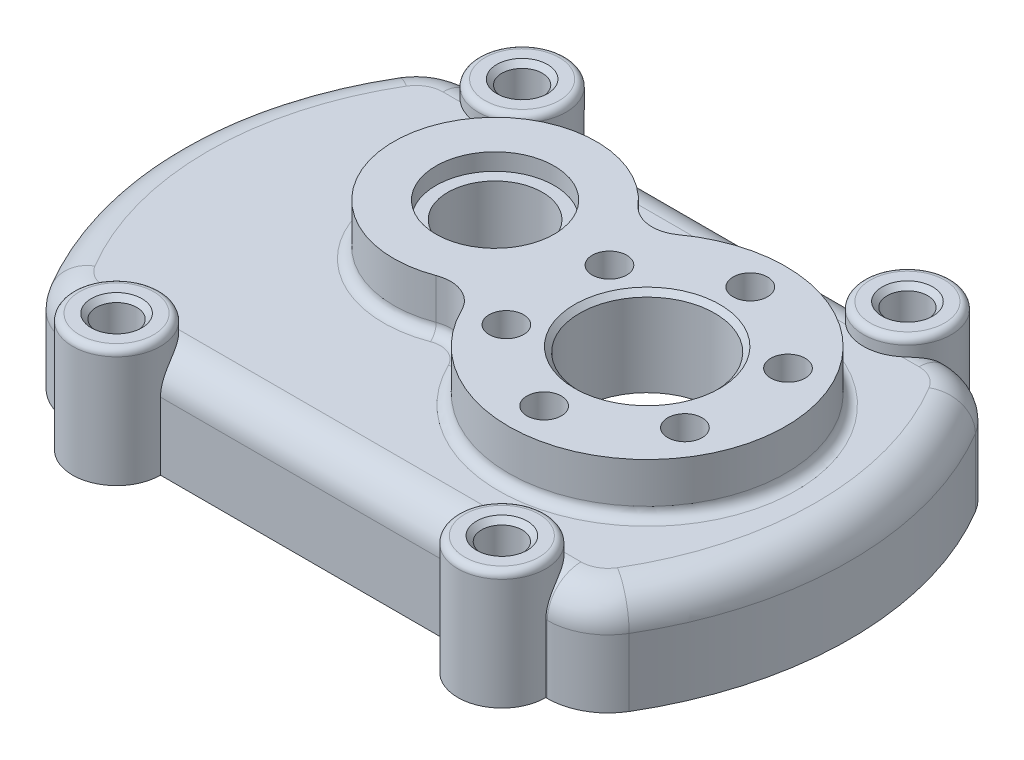
SolidWorks part; units mm, degrees
ref_plane "Piano frontale" through (0, 0, 0) normal (0, 0, 1) x (1, 0, 0)
ref_plane "Piano superiore" through (0, 0, 0) normal (0, 1, 0) x (1, 0, 0)
ref_plane "Piano destro" through (0, 0, 0) normal (1, 0, 0) x (0, 0, -1)
sketch "Schizzo2" plane through (0, 0, 0) normal (0, 1, 0) x (1, 0, 0)
  line L0 (0, 100) -> (0, -100) construction
  line L1 (-57, 100) -> (-57, -100) construction
  line L2 (57, 100) -> (57, -100) construction
  line L3 (-100, 0) -> (100, 0) construction
  line L5 (-80, -60) -> (80, -60)
  line L7 (-80, 60) -> (80, 60)
  line L9 (-80, -60) -> (80, 60) construction
  line L10 (-80, 60) -> (80, -60) construction
  arc A0 (80, 60) -> (80, -60) centre (0, 0) cw
  arc A1 (-80, 60) -> (-80, -60) centre (0, 0) ccw
  point P2 (0, 0)
  point P8 (-57, 0)
  point P9 (57, 0)
  point P12 (0, 0)
  point P13 (0, 0)
  dimension "D5" = 100
  dimension "D1" = 114
  dimension "D2" = 57
  dimension "D3" = 200
  dimension "D4" = 43
  dimension "D6" = 120
extrude "Estrusione-Estrusione3" add sketch "Schizzo2" against normal blind 30
sketch "Schizzo5" plane through (0, -30, 0) normal (0, -1, 0) x (1, 0, 0)
  line L0 (-100, 0) -> (100, 0) construction
  line L1 (-78.1665, -54) -> (78.1665, -54)
  line L3 (-78.1665, 54) -> (78.1665, 54)
  line L5 (-78.1665, -54) -> (78.1665, 54) construction
  line L6 (-78.1665, 54) -> (78.1665, -54) construction
  line L7 (-80, 60) -> (80, 60) construction
  arc A0 (-80, 60) -> (-80, -60) centre (0, 0) ccw construction
  arc A1 (78.1665, 54) -> (78.1665, -54) centre (-6, 0) cw
  arc A2 (-78.1665, 54) -> (-78.1665, -54) centre (6, 0) ccw
  point P0 (0, 0)
  point P8 (0, 0)
  point P10 (94, 0)
  point P16 (-94, 0)
  dimension "D1" = 100
  dimension "D2" = 6
  dimension "D3" = 6
extrude "Taglio-Estrusione1" cut sketch "Schizzo5" against normal blind 24
sketch "Schizzo6" plane through (0, 0, 0) normal (0, 1, 0) x (1, 0, 0)
  line L0 (-57, 100) -> (-57, -100) construction
  line L1 (-80, 60) -> (80, 60) construction
  circle A0 centre (-57, 60) radius 13
  circle A1 centre (-57, 60) radius 6
  dimension "D1" = 26
  dimension "D2" = 12
extrude "Estrusione-Estrusione4" add sketch "Schizzo6" along normal blind 5 and the other way blind 30
extrude "Taglio-Estrusione2" cut sketch "Schizzo6<3>" against normal up to next contours A1
sketch "Schizzo6<3>" plane through (0, 0, 0) normal (0, 1, 0) x (1, 0, 0) same geometry as "Schizzo6"
pattern_linear "Ripetizione a L1" count 2 spacing 114 along (1, 0, 0) of "Estrusione-Estrusione4", "Taglio-Estrusione2"
mirror "Specchia1" about plane through (0, 0, 0) normal (0, 0, 1) of "Ripetizione a L1"
sketch "Schizzo7" plane through (0, 0, 0) normal (0, 1, 0) x (1, 0, 0)
  line L0 (57, 100) -> (57, -100) construction
  line L4 (-80, 60) -> (80, 60) construction
  arc A0 (2.5862, 34.7449) -> (-9.3627, -13.0508) centre (-20, 15) ccw
  arc A1 (3.1668, -18.0087) -> (15.9748, 33.2233) centre (40, 0) ccw
  arc A2 (2.5862, 34.7449) -> (15.9748, 33.2233) centre (10.115, 41.3266) ccw
  arc A3 (-9.3627, -13.0508) -> (3.1668, -18.0087) centre (-5.8169, -22.4011) cw
  circle A6 centre (40, 0) radius 30.5 construction
  circle A7 centre (40, 0) radius 25
  circle A8 centre (-20, 15) radius 19
  dimension "D1" = 60
  dimension "D2" = 82
  dimension "D5" = 10
  dimension "D8" = 61
  dimension "D9" = 38
  dimension "D10" = 50
  dimension "D3" = 15
  dimension "D4" = 60
  dimension "D6" = 17
  dimension "D7" = 60
extrude "Estrusione-Estrusione5" add sketch "Schizzo7" along normal blind 15 contours A0 A3 A1 A2 A8 A7 region at (8.8088, 0, -29.8335)
extrude "Estrusione-Estrusione6" add sketch "Schizzo7<4>" along normal blind 15 and the other way blind 11 contours A8 | A7 region at (40, 0, 0) region at (-20, 0, -15)
sketch "Schizzo7<4>" plane through (0, 0, 0) normal (0, 1, 0) x (1, 0, 0) same geometry as "Schizzo7"
hole_wizard "Foro1" positions "Schizzo9" profile "Schizzo10" legacy end condition through all
sketch "Schizzo9" plane through (0, 15, 0) normal (0, 1, 0) x (1, 0, 0)
  point P0 (-20, 15)
sketch "Schizzo10" plane through (-20, 15, -15) normal (1, 0, 0) x (0, 0, 1)
  line L0 (0, 0) -> (0, 45)
  line L1 (0, 45) -> (14, 45)
  line L2 (14, 45) -> (14, 5)
  line L3 (14, 5) -> (17.5, 5)
  line L4 (17.5, 5) -> (17.5, 0)
  line L5 (17.5, 0) -> (0, 0)
  line L6 (0, 110) -> (0, -10) construction
  dimension "Diameter" = 28
  dimension "Depth" = 45
  dimension "C-Bore Diameter" = 35
  dimension "C-Bore Depth" = 5
hole_wizard "Foro filettato M12-1" positions "Schizzo11" profile "Schizzo12" tap size "M12" standard "ISO"
sketch "Schizzo11" plane through (0, 15, 0) normal (0, 1, 0) x (1, 0, 0)
  circle A0 centre (40, 0) radius 30.5 construction
  point P0 (40, 30.5)
sketch "Schizzo12" plane through (40, 15, -30.5) normal (1, 0, 0) x (0, 0, 1)
  line L0 (0, 0) -> (0, 18.0644)
  line L1 (0, 18.0644) -> (5.1, 15)
  line L2 (5.1, 15) -> (5.1, 0)
  line L5 (5.1, 0) -> (0, 0)
  line L10 (0, 18.0644) -> (-5.1, 15) construction
  line L11 (0, -6.35) -> (0, 107.95) construction
  dimension "Tap Drill Dia." = 10.2
  dimension "Tap Drill Depth" = 15
  dimension "Drill Angle" = 118
cosmetic thread "Filettatura del foro1" parameters "D1"=10, "D2"=12
pattern_circular "RipetizioneCircolare1" count 6 over 360 about axis through (40, 15, 0) along (0, -1, 0) of "Foro filettato M12-1"
cosmetic thread "Filettatura del foro2" parameters "D1"=10, "D2"=12
cosmetic thread "Filettatura del foro3" parameters "D1"=10, "D2"=12
cosmetic thread "Filettatura del foro4" parameters "D1"=10, "D2"=12
cosmetic thread "Filettatura del foro5" parameters "D1"=10, "D2"=12
cosmetic thread "Filettatura del foro6" parameters "D1"=10, "D2"=12
sketch "Schizzo13" plane through (0, 15, 0) normal (0, 1, 0) x (1, 0, 0)
  circle A0 centre (40, 0) radius 20
  dimension "D1" = 40
extrude "Taglio-Estrusione3" cut sketch "Schizzo13" against normal up to next
fillet "Raccordo1" radius 18 4 edges at (-80, -15, -60) (80, -15, -60) (80, -15, 60) (-80, -15, 60)
fillet "Raccordo2" radius 3 8 edges at (8.9857, 0, -31.3905) (79.7758, 0, 9.944) (-2.1375, 0, 13.1026) (-49.1043, 0, -22.2761) (94, -6, 0) (-94, -6, 0) (40, -6, 25) (-20, -6, 4)
fillet "Raccordo3" radius 10 12 edges at (70.2136, 0, 60) (79.3168, 0, 57.6517) (70.2136, 0, -60) (79.3168, 0, -57.6517) (-70.2136, 0, -60) (-79.3168, 0, -57.6517) (-70.2136, 0, 60) (-79.3168, 0, 57.6517) (0, 0, -60) (100, 0, 0) (0, 0, 60) (-100, 0, 0)
fillet "Raccordo4" radius 2 4 edges at (57, 5, -47) (-57, 5, -47) (57, 5, 47) (-57, 5, 47)
chamfer "Smusso1" distance 1.5 angle 45 5 edges at (57, 5, -54) (57, 5, 54) (-57, 5, -54) (-57, 5, 54) (40, 15, 20)
